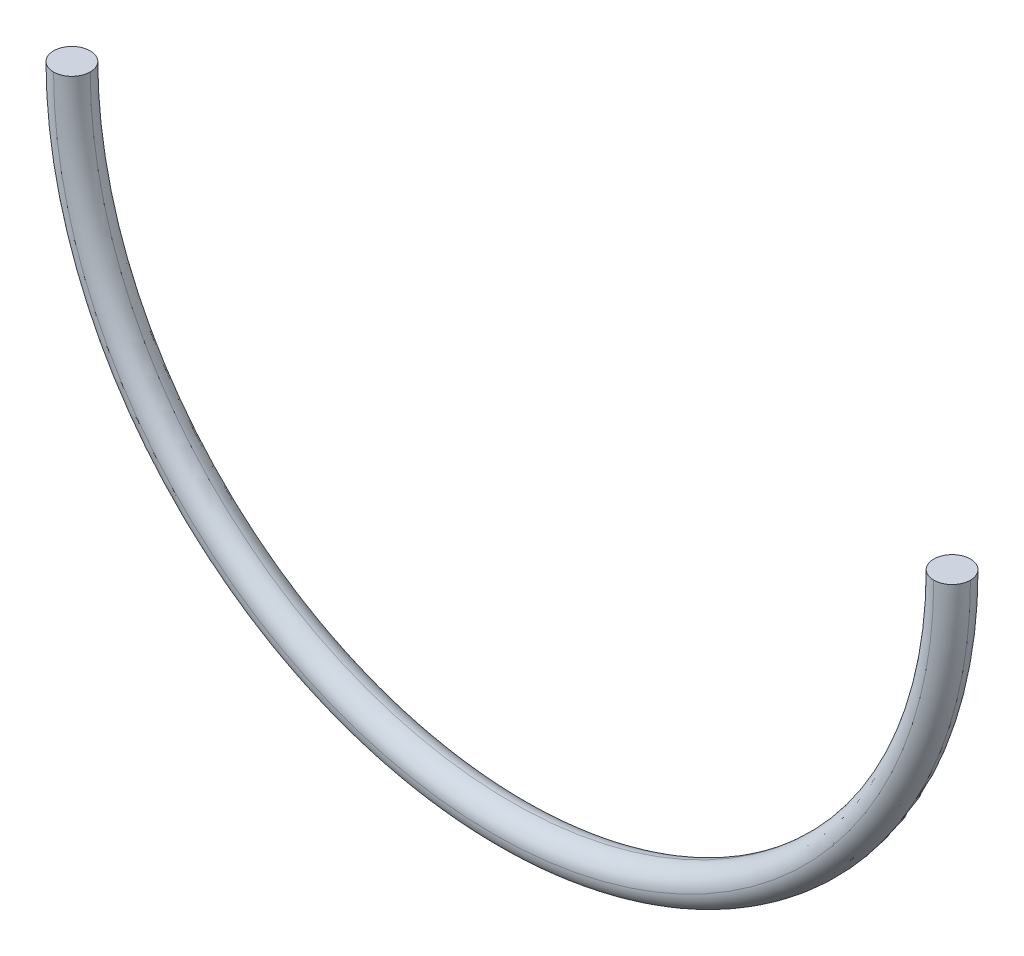
SolidWorks part; units mm, degrees
ref_plane "Front Plane" through (0, 0, 0) normal (0, 0, 1) x (1, 0, 0)
ref_plane "Top Plane" through (0, 0, 0) normal (0, 1, 0) x (1, 0, 0)
ref_plane "Right Plane" through (0, 0, 0) normal (1, 0, 0) x (0, 0, -1)
sketch "Sketch1" plane through (0, 0, 0) normal (0, 0, 1) x (1, 0, 0)
  line L0 (-75, 0) -> (-69, 0)
  line L1 (-19.9169, -60) -> (19.9169, -60)
  line L2 (-19.9169, -60) -> (-19.9169, -90)
  line L3 (-19.9169, -90) -> (19.9169, -90)
  line L4 (19.9169, -60) -> (19.9169, -90)
  line L5 (-19.9169, -60) -> (19.9169, -90) construction
  line L6 (-19.9169, -90) -> (19.9169, -60) construction
  line L13 (50, -55.9017) -> (62, -55.9017)
  line L17 (50, -55.9017) -> (50, -67.9017)
  line L18 (50, -67.9017) -> (62, -67.9017)
  line L19 (62, -55.9017) -> (62, -67.9017)
  line L20 (-50, -55.9017) -> (-62, -55.9017)
  line L21 (-50, -55.9017) -> (-50, -67.9017)
  line L22 (-50, -67.9017) -> (-62, -67.9017)
  line L23 (-62, -55.9017) -> (-62, -67.9017)
  line L24 (75, 0) -> (69, 0)
  arc A0 (-75, 0) -> (75, 0) centre (0, 0) ccw
  circle A1 centre (0, -75) radius 3
  arc A2 (-69, 0) -> (69, 0) centre (0, 0) ccw
  point P1 (0, -75)
  point P21 (0, -55.9017)
  dimension "D1" = 100
extrude "Boss-Extrude2" add sketch "Sketch1" against normal blind 6 contours A2 L4 A0 L24 | A2 L2 A0 A1 L4 | A2 L0 A0 L2 | A0 A1 region at (-72, -0.909, 0) region at (0, -70.896, 0) region at (56.1159, -41.6926, 0) region at (0, -73.716, 0)
fillet "Fillet1" radius 3 4 edges at (0, -69, -6) (0, -69, 0) (0, -75, -6) (0, -75, 0)
